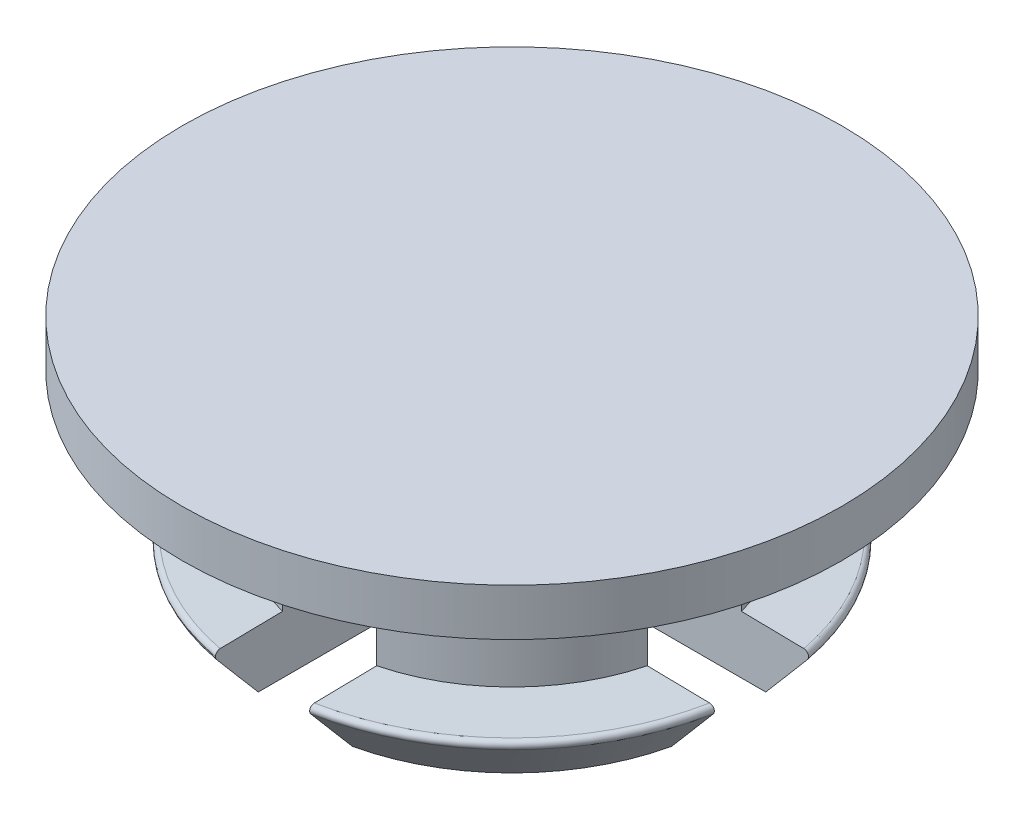
SolidWorks part; units mm, degrees
ref_plane "Front Plane" through (0, 0, 0) normal (0, 0, 1) x (1, 0, 0)
ref_plane "Top Plane" through (0, 0, 0) normal (0, 1, 0) x (1, 0, 0)
ref_plane "Right Plane" through (0, 0, 0) normal (1, 0, 0) x (0, 0, -1)
sketch "Szkic1" plane through (0, 0, 0) normal (0, 1, 0) x (1, 0, 0)
  circle A0 centre (0, 0) radius 7
  dimension "D1" = 14
extrude "Dodanie-wyciągnięcie1" add sketch "Szkic1" along normal blind 1
ref_point "Punkt1"
ref_plane "Płaszczyzna1" through (0, 0, 0) normal (0, -1, 0) x (-1, 0, 0)
sketch "Szkic2" plane through (0, 0, 0) normal (0, -1, 0) x (-1, 0, 0)
  circle A0 centre (0, 0) radius 4
  dimension "D1" = 8
extrude "Dodanie-wyciągnięcie2" add sketch "Szkic2" along normal blind 4.22
ref_axis "Oś1" through (0, -4.22, 0) along (0, 1, 0)
sketch "Szkic3" plane through (0, 0, 0) normal (1, 0, 0) x (0, 0, -1)
  line L0 (4, -4.22) -> (4.5, -4.22)
  line L1 (4.5, -4.22) -> (5.5, -3.02)
  line L2 (5.5, -3.02) -> (4, -2.9938)
  line L4 (4, -2.9938) -> (4, -4.22)
  line L5 (0, -4.22) -> (0, 0) construction
  line L6 (-7.7, 0) -> (7.7, 0) construction
  point P7 (4, -3.02)
  point P8 (4.0172, -3.02)
  dimension "D1" = 4
  dimension "D2" = 1.2
  dimension "D3" = 89
  dimension "D4" = 4.22
  dimension "D6" = 0.5
revolve "Obrót1" add sketch "Szkic3" angle 360 about axis through (0, -4.22, 0) along (0, 1, 0)
fillet "Zaokrąglenie1" radius 0.1 1 edges at (0, -3.02, -5.5)
ref_plane "Płaszczyzna2" through (0, -4.22, 0) normal (0, -1, 0) x (-1, 0, 0)
sketch "Szkic5" plane through (0, -4.22, 0) normal (0, -1, 0) x (-1, 0, 0)
  line L0 (-7.7941, -1) -> (-1, -1)
  line L1 (7.7941, 1) -> (1, 1)
  line L2 (-1, -7.7941) -> (-1, -1)
  line L3 (1, 7.7941) -> (1, 1)
  line L4 (-1, 1) -> (-1, 7.7941)
  line L5 (1, -1) -> (7.7941, -1)
  line L6 (1, -1) -> (1, -7.7941)
  line L7 (-1, 1) -> (-7.7941, 1)
  line L8 (-1, -1) -> (1, 1) construction
  arc A0 (-7.7941, 1) -> (-7.7941, -1) centre (0, 0) ccw
  arc A1 (-1, -7.7941) -> (1, -7.7941) centre (0, 0) ccw
  arc A2 (7.7941, -1) -> (7.7941, 1) centre (0, 0) ccw
  arc A3 (1, 7.7941) -> (-1, 7.7941) centre (0, 0) ccw
  point P1 (0, 0)
  dimension "D1" = 2
  dimension "D2" = 2
extrude "Wytnij-wyciągnięcie1" cut sketch "Szkic5" against normal blind 4.22
ref_plane "Płaszczyzna3" through (0, 1, 0) normal (0, 1, 0) x (1, 0, 0)
sketch "Szkic6" plane through (0, 1, 0) normal (0, 1, 0) x (1, 0, 0)
  point P0 (0, 0)
